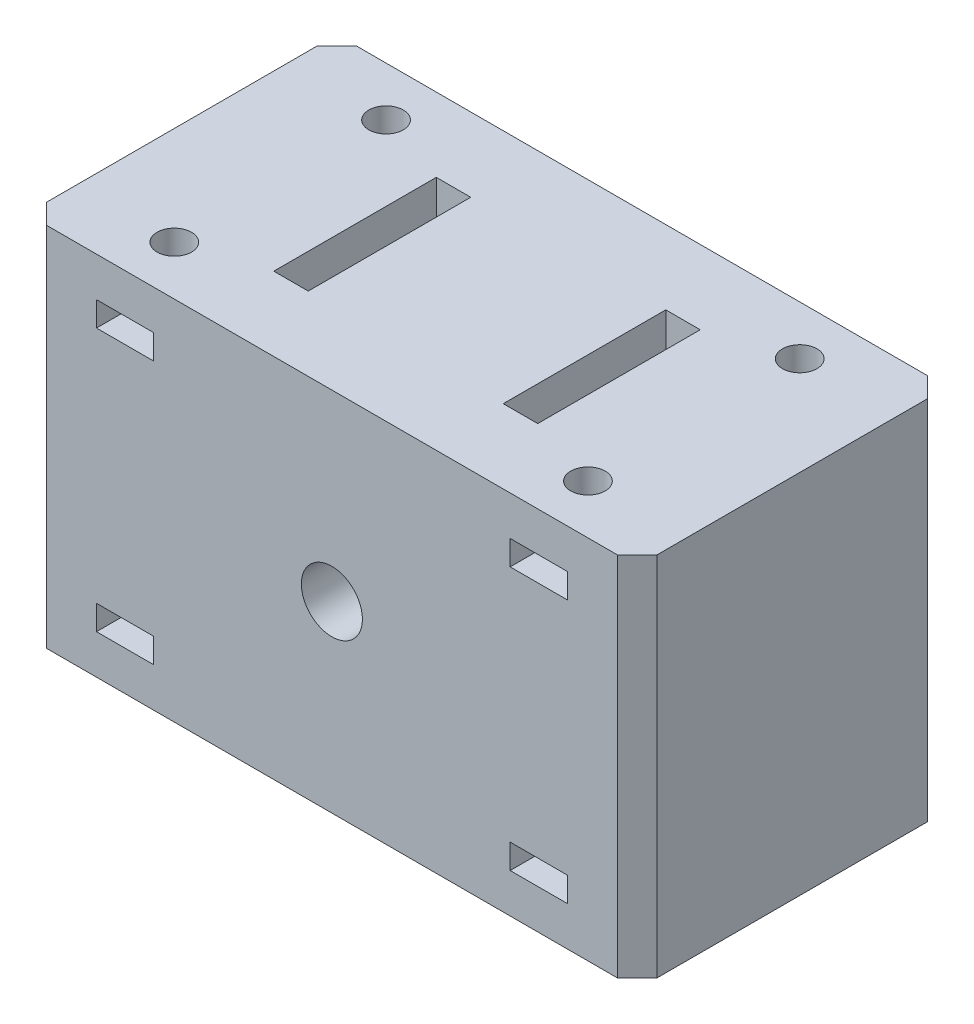
SolidWorks part; units mm, degrees
ref_plane "Front Plane" through (0, 0, 0) normal (0, 0, 1) x (1, 0, 0)
ref_plane "Top Plane" through (0, 0, 0) normal (0, 1, 0) x (1, 0, 0)
ref_plane "Right Plane" through (0, 0, 0) normal (1, 0, 0) x (0, 0, -1)
ref_plane "Plane1" through (0, -18.6, 0) normal (0, 1, 0) x (1, 0, 0)
ref_plane "Plane2" through (0, 18.6, 0) normal (0, 1, 0) x (1, 0, 0)
sketch "Sketch1" plane through (0, 18.6, 0) normal (0, 1, 0) x (1, 0, 0)
  line L0 (32, -7) -> (32, 7) construction
  line L1 (32, -7) -> (32, 7)
  line L2 (-32, 7) -> (-32, -7) construction
  line L3 (-32, 7) -> (-32, -7)
ref_plane "Plane3" through (0, 0, 15.75) normal (0, 0, 1) x (1, 0, 0)
ref_plane "Plane4" through (0, 0, -15.75) normal (0, 0, 1) x (1, 0, 0)
sketch "Sketch2" plane through (0, 0, 0) normal (0, 1, 0) x (1, 0, 0)
  line L0 (-32, 7) -> (-32, -7) construction
  line L1 (32, -7) -> (32, 7) construction
  line L2 (-32, 7) -> (-32, -7) construction
  line L3 (32, -7) -> (32, 7) construction
  line L4 (-55, 15.75) -> (55, 15.75) construction
  line L5 (-31, 15.75) -> (31, 15.75)
  line L6 (-31, 15.75) -> (-31, -15.75)
  line L7 (-31, -15.75) -> (31, -15.75)
  line L8 (31, 15.75) -> (31, -15.75)
  line L9 (-55, -15.75) -> (55, -15.75) construction
  point P12 (0, 15.75)
  dimension "D1" = 1
extrude "Boss-Extrude1" add sketch "Sketch2" along normal up to surface (18.6 mm away) and the other way up to surface (18.6 mm away) up to plane "Plane2" other way up to plane "Plane1"
sketch "Sketch3" plane through (0, 0, 0) normal (0, 0, 1) x (1, 0, 0)
  circle A0 centre (0, 0) radius 3.1
  dimension "D1" = 6.2
extrude "Cut-Extrude1" cut sketch "Sketch3" against normal through all and the other way through all
sketch "Sketch4" plane through (0, 0, 0) normal (0, 1, 0) x (1, 0, 0)
  line L1 (-21, -10.75) -> (21, -10.75) construction
  line L2 (-21, -10.75) -> (-21, 10.75) construction
  line L3 (-21, 10.75) -> (21, 10.75) construction
  line L4 (31, 15.75) -> (-31, 15.75)
  line L5 (31, -15.75) -> (31, 15.75)
  line L6 (-31, -15.75) -> (31, -15.75)
  line L7 (-31, 15.75) -> (-31, -15.75)
  line L8 (31, 15.75) -> (-31, 15.75) construction
  line L9 (31, -15.75) -> (31, 15.75) construction
  line L10 (-31, -15.75) -> (31, -15.75) construction
  line L11 (-31, 15.75) -> (-31, -15.75) construction
  line L12 (21, -10.75) -> (21, 10.75) construction
  line L13 (-21, -10.75) -> (21, 10.75) construction
  line L14 (-21, 10.75) -> (21, -10.75) construction
  circle A0 centre (-21, 10.75) radius 1.75
  circle A1 centre (21, 10.75) radius 1.75
  circle A2 centre (21, -10.75) radius 1.75
  circle A3 centre (-21, -10.75) radius 1.75
  point P2 (0, 0)
  dimension "D2" = 3.5
  dimension "D3" = 10
  dimension "D4" = 5
  dimension "D1" = 0
sketch "Sketch5" plane through (0, 18.6, 0) normal (0, 1, 0) x (1, 0, 0)
  circle A1 centre (-21, -10.75) radius 1.75
  circle A2 centre (-21, -10.75) radius 1.75
  circle A3 centre (21, -10.75) radius 1.75
  circle A4 centre (21, -10.75) radius 1.75
  circle A5 centre (21, 10.75) radius 1.75
  circle A6 centre (21, 10.75) radius 1.75
  circle A7 centre (-21, 10.75) radius 1.75
  circle A8 centre (-21, 10.75) radius 1.75
  dimension "D1" = 0
  dimension "D2" = 0
  dimension "D3" = 0
  dimension "D4" = 0
extrude "Cut-Extrude2" cut sketch "Sketch5" against normal blind 10
sketch "Sketch6" plane through (0, -18.6, 0) normal (0, -1, 0) x (1, 0, 0)
  circle A1 centre (-21, 10.75) radius 1.75
  circle A2 centre (-21, 10.75) radius 1.75
  circle A3 centre (21, 10.75) radius 1.75
  circle A4 centre (21, 10.75) radius 1.75
  circle A5 centre (21, -10.75) radius 1.75
  circle A6 centre (21, -10.75) radius 1.75
  circle A7 centre (-21, -10.75) radius 1.75
  circle A8 centre (-21, -10.75) radius 1.75
  dimension "D1" = 0
  dimension "D2" = 0
  dimension "D3" = 0
  dimension "D4" = 0
extrude "Cut-Extrude3" cut sketch "Sketch6" against normal blind 10
sketch "Sketch7" plane through (0, 18.6, 0) normal (0, 1, 0) x (1, 0, 0)
  line L0 (-21, 15.75) -> (-21, -15.75) construction
  line L1 (31, 15.75) -> (-31, 15.75) construction
  line L2 (-31, -15.75) -> (31, -15.75) construction
  line L3 (21, 15.75) -> (21, -15.75) construction
  line L4 (-21, -10.75) -> (-21, 10.75) construction
  line L5 (21, -10.75) -> (21, 10.75) construction
  line L6 (31, 15.75) -> (-31, 15.75) construction
  line L7 (-23.9, 15.75) -> (-18.1, 15.75)
  line L8 (-23.9, 15.75) -> (-23.9, 6.75)
  line L9 (-23.9, 6.75) -> (-18.1, 6.75)
  line L10 (-18.1, 15.75) -> (-18.1, 6.75)
  line L11 (-21, 0) -> (21, 0) construction
  line L12 (0, 10.75) -> (0, -10.75) construction
  line L13 (-21, 10.75) -> (21, 10.75) construction
  line L14 (-21, -10.75) -> (21, -10.75) construction
  line L15 (0, -17.325) -> (0, 17.325) construction
  line L16 (23.9, 6.75) -> (18.1, 6.75)
  line L17 (18.1, 15.75) -> (18.1, 6.75)
  line L18 (23.9, 15.75) -> (18.1, 15.75)
  line L19 (23.9, 15.75) -> (23.9, 6.75)
  line L20 (-20.46, 0) -> (20.46, 0) construction
  line L21 (23.9, -15.75) -> (23.9, -6.75)
  line L22 (23.9, -15.75) -> (18.1, -15.75)
  line L23 (18.1, -15.75) -> (18.1, -6.75)
  line L24 (23.9, -6.75) -> (18.1, -6.75)
  line L25 (-23.9, -6.75) -> (-18.1, -6.75)
  line L26 (-18.1, -15.75) -> (-18.1, -6.75)
  line L27 (-23.9, -15.75) -> (-18.1, -15.75)
  line L28 (-23.9, -15.75) -> (-23.9, -6.75)
  point P19 (-21, 6.75)
  point P20 (-21, 10.75)
  dimension "D1" = 5.8
  dimension "D2" = 4
extrude "Cut-Extrude4" cut sketch "Sketch7" against normal blind 2.5 from offset 4 offset against normal yes
sketch "Sketch8" plane through (0, -18.6, 0) normal (0, -1, 0) x (1, 0, 0)
  line L4 (-23.9, -15.75) -> (-18.1, -15.75)
  line L5 (-18.1, -15.75) -> (-18.1, -6.75)
  line L6 (-18.1, -6.75) -> (-23.9, -6.75)
  line L7 (-23.9, -6.75) -> (-23.9, -15.75)
  line L8 (-23.9, -15.75) -> (-18.1, -15.75)
  line L9 (-18.1, -15.75) -> (-18.1, -6.75)
  line L10 (-18.1, -6.75) -> (-23.9, -6.75)
  line L11 (-23.9, -6.75) -> (-23.9, -15.75)
  line L12 (-23.9, 6.75) -> (-18.1, 6.75)
  line L13 (-18.1, 6.75) -> (-18.1, 15.75)
  line L14 (-18.1, 15.75) -> (-23.9, 15.75)
  line L15 (-23.9, 15.75) -> (-23.9, 6.75)
  line L16 (-23.9, 6.75) -> (-18.1, 6.75)
  line L17 (-18.1, 6.75) -> (-18.1, 15.75)
  line L18 (-18.1, 15.75) -> (-23.9, 15.75)
  line L19 (-23.9, 15.75) -> (-23.9, 6.75)
  line L20 (23.9, 6.75) -> (23.9, 15.75)
  line L21 (18.1, 6.75) -> (23.9, 6.75)
  line L22 (18.1, 15.75) -> (18.1, 6.75)
  line L23 (23.9, 15.75) -> (18.1, 15.75)
  line L24 (23.9, 6.75) -> (23.9, 15.75)
  line L25 (18.1, 6.75) -> (23.9, 6.75)
  line L26 (18.1, 15.75) -> (18.1, 6.75)
  line L27 (23.9, 15.75) -> (18.1, 15.75)
  line L28 (23.9, -6.75) -> (18.1, -6.75)
  line L29 (18.1, -6.75) -> (18.1, -15.75)
  line L30 (18.1, -15.75) -> (23.9, -15.75)
  line L31 (23.9, -15.75) -> (23.9, -6.75)
  line L32 (23.9, -6.75) -> (18.1, -6.75)
  line L33 (18.1, -6.75) -> (18.1, -15.75)
  line L34 (18.1, -15.75) -> (23.9, -15.75)
  line L35 (23.9, -15.75) -> (23.9, -6.75)
  dimension "D1" = 0
  dimension "D2" = 0
  dimension "D3" = 0
  dimension "D4" = 0
extrude "Cut-Extrude5" cut sketch "Sketch8" against normal blind 2.5 from offset 4 offset against normal yes
chamfer "Chamfer1" distance 2 angle 45 4 edges at (-31, 0, -15.75) (31, 0, -15.75) (-31, 0, 15.75) (31, 0, 15.75)
sketch "Sketch9" plane through (0, 0, 0) normal (0, 0, 1) x (1, 0, 0)
  line L0 (0, -3.1) -> (0, -5.1) construction
  line L1 (1, -5.1) -> (-1, -5.1) construction
  circle A1 centre (0, 0) radius 3.1
  circle A2 centre (0, 0) radius 3.1 construction
  point P0 (0, -3.1)
  point P9 (0, -5.1)
  dimension "D2" = 2
  dimension "D1" = 0
ref_plane "Plane5" through (0, -5.1, 0) normal (0, 1, 0) x (1, 0, 0)
sketch "Sketch10" plane through (0, 18.6, 0) normal (0, 1, 0) x (1, 0, 0)
  line L0 (-13.4, -8.25) -> (-9.9, -8.25)
  line L1 (-9.9, -8.25) -> (-9.9, 8.25)
  line L2 (-9.9, 8.25) -> (-13.4, 8.25)
  line L3 (-13.4, 8.25) -> (-13.4, -8.25)
  line L4 (-12.9, -7.75) -> (-10.4, -7.75)
  line L5 (-10.4, -7.75) -> (-10.4, 7.75)
  line L6 (-10.4, 7.75) -> (-12.9, 7.75)
  line L7 (-12.9, 7.75) -> (-12.9, -7.75)
  line L8 (-12.9, -7.75) -> (-10.4, -7.75) construction
  line L9 (-10.4, -7.75) -> (-10.4, 7.75) construction
  line L10 (-10.4, 7.75) -> (-12.9, 7.75) construction
  line L11 (-12.9, 7.75) -> (-12.9, -7.75) construction
  line L12 (10.4, -7.75) -> (12.9, -7.75)
  line L13 (12.9, -7.75) -> (12.9, 7.75)
  line L14 (12.9, 7.75) -> (10.4, 7.75)
  line L15 (10.4, 7.75) -> (10.4, -7.75)
  line L16 (10.4, -7.75) -> (12.9, -7.75) construction
  line L17 (12.9, -7.75) -> (12.9, 7.75) construction
  line L18 (12.9, 7.75) -> (10.4, 7.75) construction
  line L19 (10.4, 7.75) -> (10.4, -7.75) construction
  line L20 (9.9, -8.25) -> (13.4, -8.25)
  line L21 (13.4, -8.25) -> (13.4, 8.25)
  line L22 (13.4, 8.25) -> (9.9, 8.25)
  line L23 (9.9, 8.25) -> (9.9, -8.25)
  dimension "D1" = 0
  dimension "D2" = 0
  dimension "D3" = 0.5
extrude "Cut-Extrude6" cut sketch "Sketch10" against normal through all
sketch "Sketch11" plane through (0, -5.1, 0) normal (0, 1, 0) x (1, 0, 0)
  line L0 (13.4, -13.4) -> (13.4, 13.4)
  line L1 (13.4, 13.4) -> (-13.4, 13.4)
  line L2 (-13.4, 13.4) -> (-13.4, -13.4)
  line L3 (-13.4, -13.4) -> (13.4, -13.4)
  line L4 (13, -13) -> (13, 13)
  line L5 (13, 13) -> (-13, 13)
  line L6 (-13, 13) -> (-13, -13)
  line L7 (-13, -13) -> (13, -13)
  line L8 (13, -13) -> (13, 13) construction
  line L9 (13, 13) -> (-13, 13) construction
  line L10 (-13, 13) -> (-13, -13) construction
  line L11 (-13, -13) -> (13, -13) construction
  dimension "D1" = 0
  dimension "D2" = 0.4
extrude "Cut-Extrude7" cut sketch "Sketch11" against normal through all
sketch "Sketch12" plane through (0, -5.1, 0) normal (0, -1, 0) x (1, 0, 0)
  circle A0 centre (-10.3, -10.3) radius 1.7 construction
  circle A1 centre (10.3, -10.3) radius 1.7 construction
  circle A2 centre (-10.3, 10.3) radius 1.7 construction
  circle A3 centre (10.3, 10.3) radius 1.7 construction
  circle A4 centre (-10.3, -10.3) radius 1.7
  circle A5 centre (10.3, -10.3) radius 1.7
  circle A6 centre (-10.3, 10.3) radius 1.7
  circle A7 centre (10.3, 10.3) radius 1.7
sketch "Sketch13" plane through (0, -5.1, 0) normal (0, -1, 0) x (1, 0, 0)
  line L0 (-8.05, -10.3) -> (-8.05, -13.4) construction
  line L1 (8.05, -10.3) -> (8.05, -13.4) construction
  line L2 (8.05, 10.3) -> (8.05, 13.4) construction
  line L3 (-8.05, 10.3) -> (-8.05, 13.4) construction
  line L4 (8.05, -13.4) -> (13.4, -13.4) construction
  line L5 (9.9, 8.0858) -> (9.9, 8.25) construction
  line L6 (-9.9, -8.0858) -> (-9.9, -8.25) construction
  line L7 (-8.05, 13.4) -> (-13.4, 13.4) construction
  line L8 (0, 4.8363) -> (0, -5.3295) construction
  line L9 (-3.4212, 0) -> (2.9702, 0) construction
  line L10 (-9.9, -8.25) -> (-8.25, -9.9)
  line L11 (-8.25, -9.9) -> (-8.25, -13.4)
  line L12 (9.9, -8.25) -> (9.9, 8.25)
  line L13 (9.9, 8.25) -> (13.4, 8.25)
  line L14 (13.4, 8.25) -> (13.4, 13.4)
  line L15 (13.4, 13.4) -> (-13.4, 13.4)
  line L16 (-13.4, 13.4) -> (-13.4, 8.25)
  line L17 (-13.4, 8.25) -> (-9.9, 8.25)
  line L18 (-9.9, 8.25) -> (-9.9, -8.25)
  line L19 (-9.9, -8.25) -> (-13.4, -8.25)
  line L20 (-13.4, -8.25) -> (-13.4, -13.4)
  line L21 (-13.4, -13.4) -> (13.4, -13.4)
  line L22 (13.4, -13.4) -> (13.4, -8.25)
  line L23 (13.4, -8.25) -> (9.9, -8.25)
  line L24 (9.9, -8.25) -> (9.9, -8.0858) construction
  line L25 (9.9, 8.25) -> (13.4, 8.25) construction
  line L26 (13.4, 8.25) -> (13.4, 13.4) construction
  line L27 (13.4, 13.4) -> (8.05, 13.4) construction
  line L28 (-13.4, 13.4) -> (-13.4, 8.25) construction
  line L29 (-13.4, 8.25) -> (-9.9, 8.25) construction
  line L30 (-9.9, 8.25) -> (-9.9, 8.0858) construction
  line L31 (-9.9, -8.25) -> (-13.4, -8.25)
  line L32 (-13.4, -8.25) -> (-13.4, -13.4)
  line L33 (-13.4, -13.4) -> (-8.05, -13.4) construction
  line L34 (13.4, -13.4) -> (13.4, -8.25) construction
  line L35 (13.4, -8.25) -> (9.9, -8.25) construction
  line L36 (-8.25, -13.4) -> (-13.4, -13.4)
  line L37 (9.9, -8.25) -> (8.25, -9.9)
  line L38 (8.25, -9.9) -> (8.25, -13.4)
  line L39 (8.25, -13.4) -> (13.4, -13.4)
  line L40 (13.4, -8.25) -> (13.4, -13.4)
  line L41 (9.9, -8.25) -> (13.4, -8.25)
  line L42 (-9.9, 8.25) -> (-8.25, 9.9)
  line L43 (-8.25, 9.9) -> (-8.25, 13.4)
  line L44 (-8.25, 13.4) -> (-13.4, 13.4)
  line L45 (-13.4, 8.25) -> (-13.4, 13.4)
  line L46 (-9.9, 8.25) -> (-13.4, 8.25)
  line L47 (9.9, 8.25) -> (13.4, 8.25)
  line L48 (13.4, 8.25) -> (13.4, 13.4)
  line L49 (8.25, 13.4) -> (13.4, 13.4)
  line L50 (8.25, 9.9) -> (8.25, 13.4)
  line L51 (9.9, 8.25) -> (8.25, 9.9)
  arc A0 (-8.05, -10.3) -> (-9.9, -8.0858) centre (-10.3, -10.3) ccw construction
  circle A1 centre (10.3, 10.3) radius 1.7
  circle A2 centre (10.3, 10.3) radius 1.7 construction
  circle A3 centre (-10.3, 10.3) radius 1.7
  circle A4 centre (-10.3, 10.3) radius 1.7 construction
  circle A5 centre (10.3, -10.3) radius 1.7
  circle A6 centre (10.3, -10.3) radius 1.7 construction
  circle A7 centre (-10.3, -10.3) radius 1.7
  circle A8 centre (-10.3, -10.3) radius 1.7 construction
  arc A9 (-9.9, 8.0858) -> (-8.05, 10.3) centre (-10.3, 10.3) ccw construction
  arc A10 (8.05, 10.3) -> (9.9, 8.0858) centre (10.3, 10.3) ccw construction
  arc A11 (9.9, -8.0858) -> (8.05, -10.3) centre (10.3, -10.3) ccw construction
  circle A12 centre (-10.3, 10.3) radius 1 construction
  circle A13 centre (10.3, 10.3) radius 1 construction
  circle A14 centre (-10.3, -10.3) radius 1 construction
  circle A15 centre (10.3, -10.3) radius 1 construction
  dimension "D5" = 4.5
  dimension "D7" = 2
  dimension "D8" = 45
  dimension "D1" = 0
  dimension "D2" = 0
  dimension "D3" = 0
  dimension "D4" = 0
  dimension "D6" = 0
extrude "Boss-Extrude2" add sketch "Sketch13" along normal up to surface (3 mm away)
sketch "Sketch14" plane through (0, -8.1, 0) normal (0, -1, 0) x (1, 0, 0)
  circle A0 centre (10.3, -10.3) radius 1 construction
  circle A1 centre (-10.3, -10.3) radius 1 construction
  circle A2 centre (-10.3, 10.3) radius 1 construction
  circle A3 centre (10.3, 10.3) radius 1 construction
  circle A4 centre (10.3, -10.3) radius 1
  circle A5 centre (-10.3, -10.3) radius 1
  circle A6 centre (-10.3, 10.3) radius 1
  circle A7 centre (10.3, 10.3) radius 1
extrude "Cut-Extrude8" cut sketch "Sketch14" against normal blind 5
